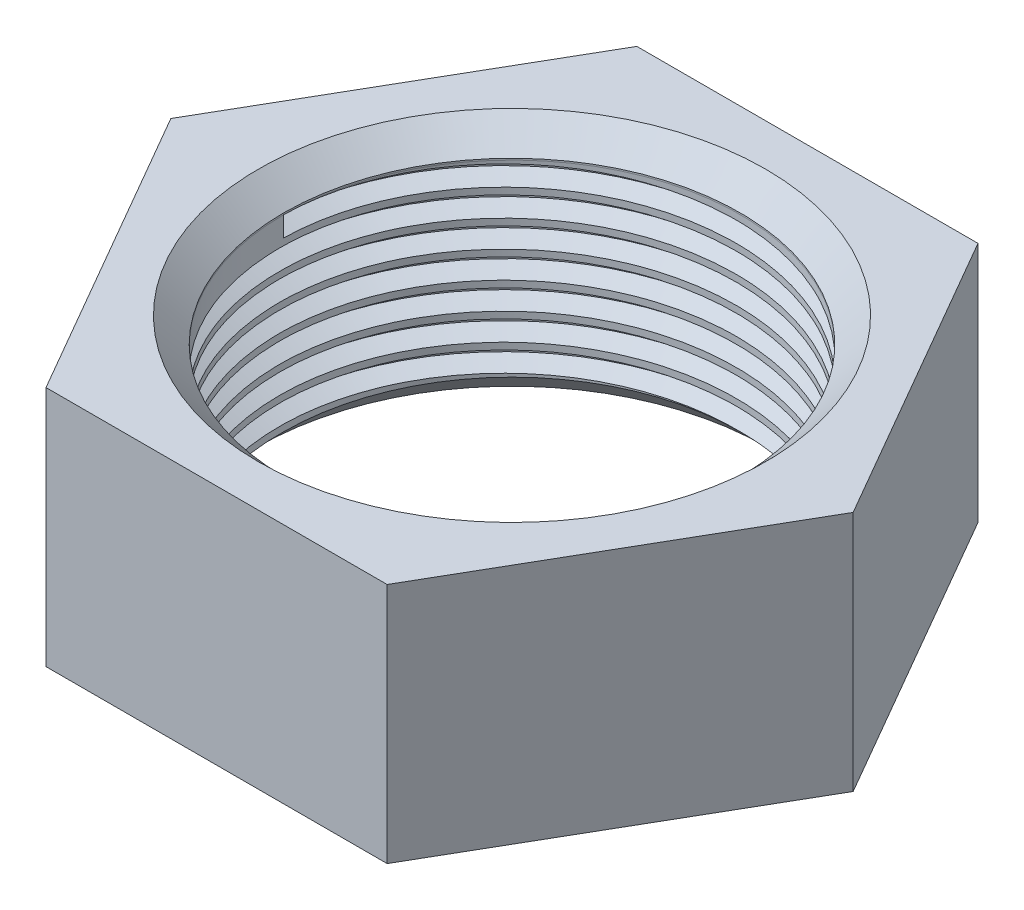
SolidWorks part; units mm, degrees
ref_plane "Front Plane" through (0, 0, 0) normal (0, 0, 1) x (1, 0, 0)
ref_plane "Top Plane" through (0, 0, 0) normal (0, 1, 0) x (1, 0, 0)
ref_plane "Right Plane" through (0, 0, 0) normal (1, 0, 0) x (0, 0, -1)
sketch "Sketch2" plane through (0, 0, 0) normal (0, 1, 0) x (1, 0, 0)
  line L1 (12.7017, 0) -> (6.3509, 11)
  line L2 (6.3509, 11) -> (-6.3509, 11)
  line L3 (-6.3509, 11) -> (-12.7017, 0)
  line L4 (-12.7017, 0) -> (-6.3509, -11)
  line L5 (-6.3509, -11) -> (6.3509, -11)
  line L6 (6.3509, -11) -> (12.7017, 0)
  circle A0 centre (0, 0) radius 11 construction
  dimension "D1" = 22
extrude "Boss-Extrude1" add sketch "Sketch2" along normal blind 9
sketch "Sketch3" plane through (0, 0, 0) normal (1, 0, 0) x (0, 0, -1)
  line L0 (0, 9) -> (0, 0) construction
  line L3 (8.5, 8) -> (8.5, 0)
  line L4 (0, 0) -> (11, 0) construction
  line L5 (8.5, 0) -> (0, 0)
  line L6 (0, 0) -> (0, 16.5)
  arc A0 (8.5, 8) -> (0, 16.5) centre (0, 8) ccw
  dimension "D1" = 8.5
  dimension "D2" = 8
revolve "Cut-Revolve1" cut sketch "Sketch3" angle 360 about L6
thread "Thread1" pitch 1 start angle 0, offset 0, length 0, pitch 1, diameter 17
ref_plane "Plane4" through (-8.5, 8, 0) normal (0, 0, 1) x (-1, 0, 0)
sketch "Thread Profile4" plane through (-8.5, 8, 0) normal (0, 0, 1) x (-1, 0, 0)
  line L0 (0, 0) -> (0, 1) construction
  line L1 (0, 0) -> (0.5413, 0.3125)
  line L2 (0.5413, 0.3125) -> (0.5413, 0.4375)
  line L3 (0.5413, 0.4375) -> (0, 0.75)
  line L4 (0.5413, 0.375) -> (0, 0.375) construction
  line L11 (0, 0) -> (0, 0.75)
  point P2 (0, 0)
  dimension "Pitch" = 1
  dimension "Profile_Angle" = 60
  dimension "Profile_Land" = 0.125
  dimension "Profile_Height" = 0.5413
chamfer "Chamfer1" distance 1 angle 45 2 edges at (0, 9, 8.441) (0, 0, -8.5)
